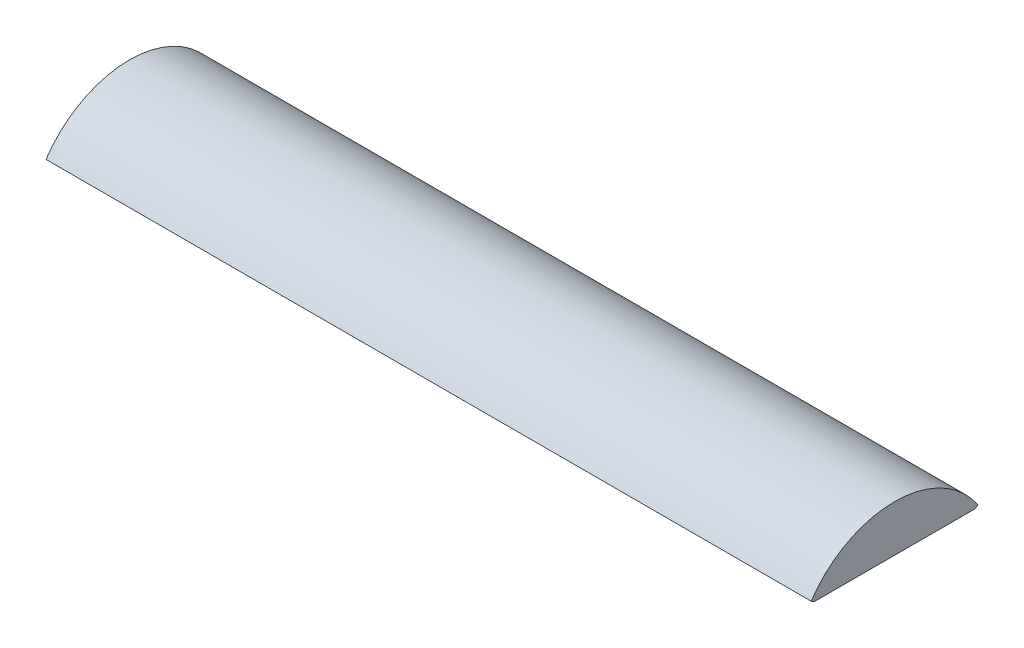
SolidWorks part; units mm, degrees
ref_plane "Alzado" through (0, 0, 0) normal (0, 0, 1) x (1, 0, 0)
ref_plane "Planta" through (0, 0, 0) normal (0, 1, 0) x (1, 0, 0)
ref_plane "Vista lateral" through (0, 0, 0) normal (1, 0, 0) x (0, 0, -1)
sketch "Croquis2" plane through (0, 0, 0) normal (1, 0, 0) x (0, 0, -1)
  line L0 (55, 0) -> (-55, 0) construction
  arc A0 (-64.1784, 0) -> (8.3216, 0) centre (-27.9284, -24.2929) cw
  dimension "D2" = 72.5
extrude "Extruir-Lámina1" add sketch "Croquis2" along normal blind 332.5 thin thin type one direction wall 1.5
sketch "Croquis3" plane through (0, 0, 0) normal (-1, 0, 0) x (0, 0, 1)
  line L0 (-7.0755, -0.8351) -> (62.9323, -0.8351)
  arc A0 (-7.0755, -0.8351) -> (62.9323, -0.8351) centre (27.9284, -24.2929) cw
extrude "Saliente-Extruir1" add sketch "Croquis3" against normal blind 0.5
sketch "Croquis4" plane through (332.5, 0, 0) normal (1, 0, 0) x (0, 0, -1)
  line L0 (-62.9323, -0.8351) -> (7.0755, -0.8351)
  arc A0 (-62.9323, -0.8351) -> (7.0755, -0.8351) centre (-27.9284, -24.2929) cw
extrude "Saliente-Extruir2" add sketch "Croquis4" against normal blind 0.5
